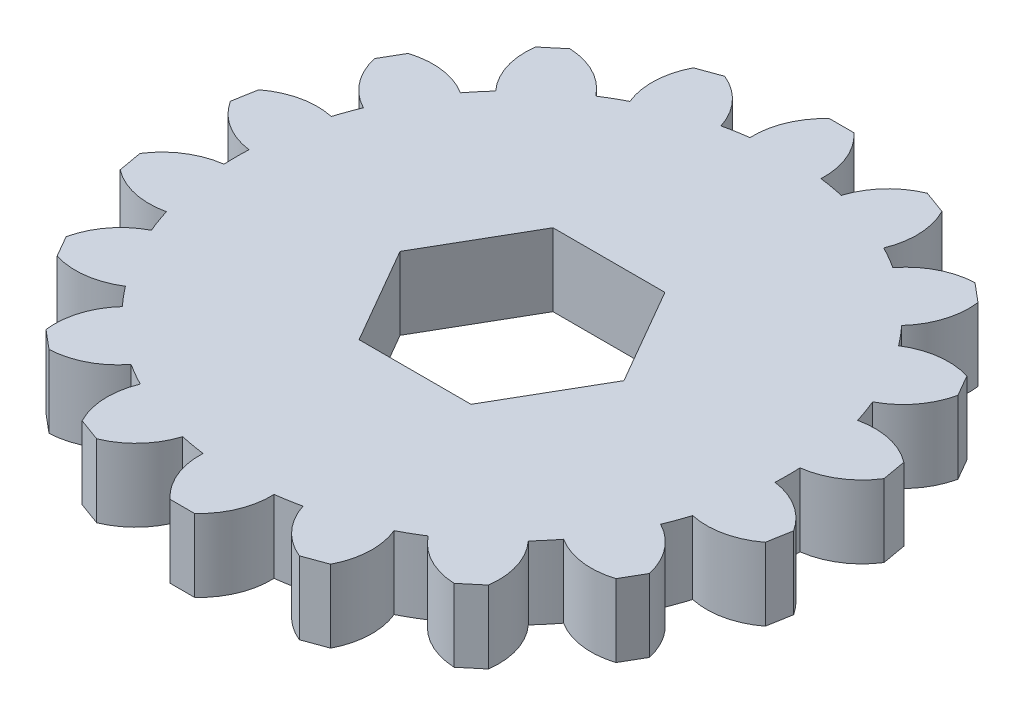
SolidWorks part; units mm, degrees
ref_plane "Front Plane" through (0, 0, 0) normal (0, 0, 1) x (1, 0, 0)
ref_plane "Top Plane" through (0, 0, 0) normal (0, 1, 0) x (1, 0, 0)
ref_plane "Right Plane" through (0, 0, 0) normal (1, 0, 0) x (0, 0, -1)
sketch "Sketch2" plane through (0, 0, 0) normal (0, 1, 0) x (1, 0, 0)
  line L1 (7.3323, 0) -> (3.6662, 6.35)
  line L2 (3.6662, 6.35) -> (-3.6662, 6.35)
  line L3 (-3.6662, 6.35) -> (-7.3323, 0)
  line L4 (-7.3323, 0) -> (-3.6662, -6.35)
  line L5 (-3.6662, -6.35) -> (3.6662, -6.35)
  line L6 (3.6662, -6.35) -> (7.3323, 0)
  circle A0 centre (0, 0) radius 18.0641
  circle A1 centre (0, 0) radius 6.35 construction
  dimension "D1" = 36.1282
  dimension "D2" = 12.7
  dimension "D3" = 6.35
extrude "Boss-Extrude2" add sketch "Sketch2" along normal blind 4.7625
sketch "Sketch1" plane through (0, 0, 0) normal (0, 1, 0) x (1, 0, 0)
  line L0 (0, 0) -> (-3.808, 21.596) construction
  line L1 (0, 0) -> (3.808, 21.596) construction
  line L2 (3.808, 21.596) -> (-3.808, 21.596) construction
  line L3 (-0.8013, 21.596) -> (0.8013, 21.596)
  line L4 (1.9721, 19.9239) -> (0.8013, 21.596) construction
  line L5 (-1.9721, 19.9239) -> (-2.3266, 17.9137) construction
  line L6 (-1.9721, 19.9239) -> (-0.8013, 21.596) construction
  line L7 (1.9721, 19.9239) -> (2.3266, 17.9137) construction
  line L8 (0, 21.596) -> (0, 0) construction
  circle A0 centre (0, 0) radius 18.0641
  arc A1 (-3.1368, 17.7897) -> (3.1368, 17.7897) centre (0, 0) cw
  arc A2 (-0.8013, 21.596) -> (-2.3266, 17.9137) centre (2.3844, 18.1194) ccw
  arc A3 (0.8013, 21.596) -> (2.3266, 17.9137) centre (-2.3844, 18.1194) cw
  point P6 (0, 21.596)
  point P11 (0, 21.596)
  point P18 (-1.9721, 19.9239)
  point P19 (0, 0)
  point P20 (0, 0)
  point P21 (0, 0)
  point P23 (0, 0)
  point P24 (0, 0)
  point P25 (0, 0)
  point P26 (0, 0)
  point P27 (0, 0)
  point P28 (0, 0)
  point P29 (0, 0)
  point P31 (3.7274, 21.2866)
  dimension "D1" = 36.1283
  dimension "D2" = 20
  dimension "D6" = 10
  dimension "D7" = 35
  dimension "D3" = 6.3056
  dimension "D4" = 4.25
  dimension "D5" = 2.6
extrude "Boss-Extrude3" add sketch "Sketch1" along normal blind 4.7625 contours A3 L3 A2 A1 region at (0, 0, -19.572)
pattern_circular "CirPattern1" count 18 over 360 about axis through (0, 4.7625, 0) along (0, -1, 0) of "Boss-Extrude3"
